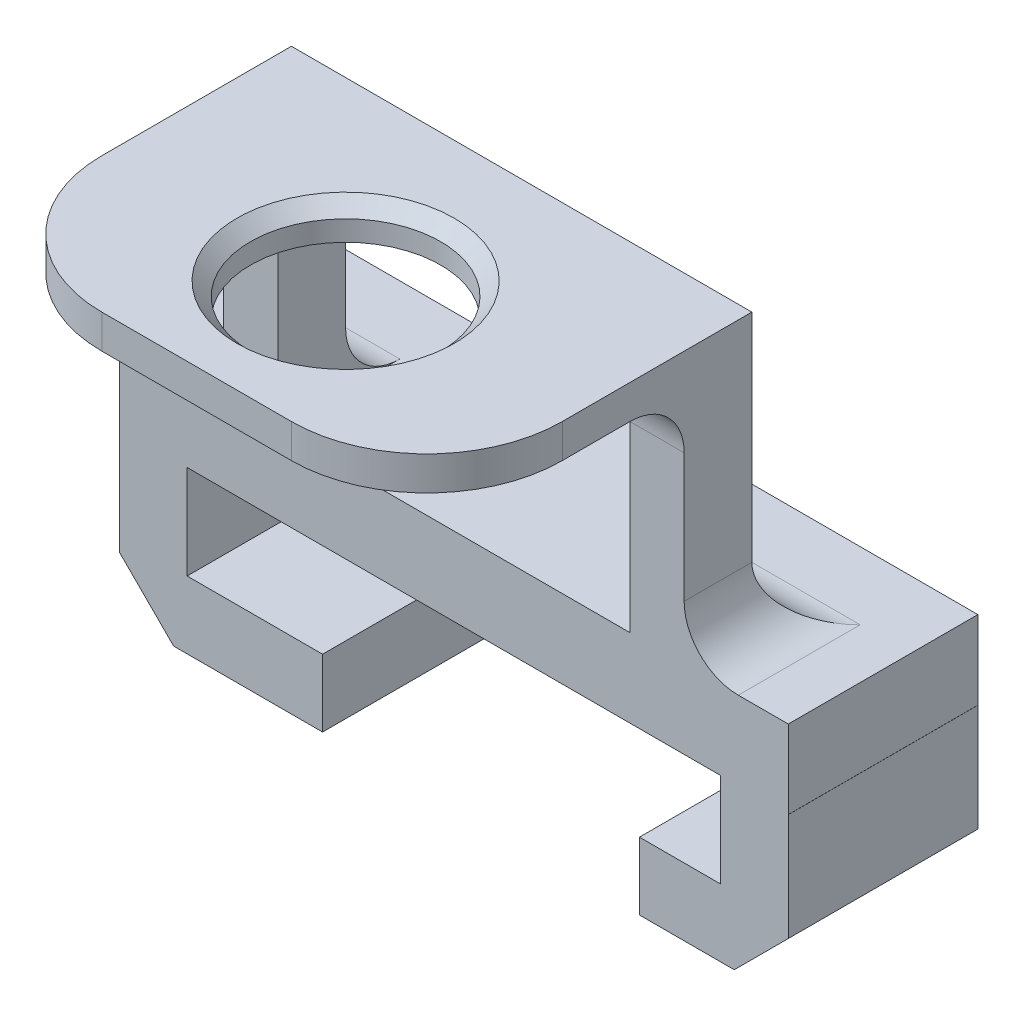
SolidWorks part; units mm, degrees
ref_plane "Front Plane" through (0, 0, 0) normal (0, 0, 1) x (1, 0, 0)
ref_plane "Top Plane" through (0, 0, 0) normal (0, 1, 0) x (1, 0, 0)
ref_plane "Right Plane" through (0, 0, 0) normal (1, 0, 0) x (0, 0, -1)
sketch "Sketch2" plane through (0, 0, 0) normal (0, 0, 1) x (1, 0, 0)
  line L0 (12.3453, 19.45) -> (-12.3453, 19.45)
  line L1 (12.3453, 22.3446) -> (-12.3453, 22.3446)
  line L2 (12.3453, 19.45) -> (12.3453, 22.3446)
  line L8 (-12.3453, 19.45) -> (-12.3453, 22.3446)
  dimension "D2" = 2.8946
extrude "Boss-Extrude2" add sketch "Sketch2" along normal blind 5
extrude "Boss-Extrude3" add sketch "Sketch2<2>" against normal blind 2
sketch "Sketch2<2>" plane through (0, 0, 0) normal (0, 0, 1) x (1, 0, 0) same geometry as "Sketch2"
ref_plane "Plane4" through (0, 0, 5) normal (0, 0, 1) x (1, 0, 0)
ref_plane "Plane6" through (0, 19.45, 0) normal (0, -1, 0) x (-1, 0, 0)
sketch "Sketch8" plane through (0, 19.45, 0) normal (0, -1, 0) x (-1, 0, 0)
  line L1 (-8.5825, -5) -> (8.5825, -5) construction
  line L2 (12.35, 2) -> (9.85, 2)
  line L3 (12.3453, 2) -> (-12.3453, 2) construction
  line L4 (-9.85, 2) -> (-9.85, -5)
  line L5 (-9.85, -5) -> (-12.35, -5)
  line L6 (-12.35, -5) -> (-12.35, 2)
  line L7 (-12.35, 2) -> (-9.85, 2)
  line L8 (12.35, -5) -> (12.35, 2)
  line L9 (9.85, -5) -> (12.35, -5)
  line L10 (9.85, 2) -> (9.85, -5)
  point P0 (0, 0)
  dimension "D1" = 9.85
  dimension "D2" = 9.85
  dimension "D3" = 2.5
  dimension "D4" = 2.5
extrude "Boss-Extrude4" add sketch "Sketch8" along normal blind 5.96
ref_plane "Plane7" through (9.85, 0, 0) normal (-1, 0, 0) x (0, 0, 1)
sketch "Sketch10" plane through (9.85, 0, 0) normal (-1, 0, 0) x (0, 0, 1)
  line L0 (5, 13.49) -> (-2, 13.49) construction
  line L1 (5, 13.49) -> (-2, 13.49)
  line L2 (5, 13.49) -> (5, 15.98)
  line L3 (5, 15.98) -> (-2, 15.98)
  line L4 (-2, 13.49) -> (-2, 15.98)
  line L5 (-2, 13.49) -> (-2, 19.45) construction
  dimension "D1" = 2.49
extrude "Boss-Extrude5" add sketch "Sketch10" along normal blind 3
ref_plane "Plane8" through (-9.85, 0, 0) normal (1, 0, 0) x (0, 0, -1)
sketch "Sketch11" plane through (-9.85, 0, 0) normal (1, 0, 0) x (0, 0, -1)
  line L0 (2, 13.49) -> (2, 19.45) construction
  line L1 (-5, 13.49) -> (2, 13.49)
  line L2 (-5, 13.49) -> (-5, 15.98)
  line L3 (-5, 15.98) -> (2, 15.98)
  line L4 (2, 13.49) -> (2, 15.98)
  dimension "D1" = 2.49
extrude "Boss-Extrude6" add sketch "Sketch11" along normal blind 5
ref_plane "Plane9" through (0, 22.3446, 0) normal (0, 1, 0) x (1, 0, 0)
sketch "Sketch12" plane through (0, 22.3446, 0) normal (0, 1, 0) x (1, 0, 0)
  line L3 (12.3453, -5) -> (-12.3453, -5) construction
  line L4 (8.5, -5) -> (-8.5, -5)
  line L5 (8.5, -5) -> (8.5, -2.5)
  line L6 (8.5, -2.5) -> (-8.5, -2.5)
  line L7 (-8.5, -5) -> (-8.5, -2.5)
  point P6 (0, 0)
  dimension "D1" = 17
  dimension "D2" = 8.5
  dimension "D3" = 2.5
extrude "Boss-Extrude7" add sketch "Sketch12" along normal blind 10
ref_plane "Plane10" through (0, 0, 5) normal (0, 0, 1) x (1, 0, 0)
sketch "Sketch14" plane through (0, 0, 5) normal (0, 0, 1) x (1, 0, 0)
  line L0 (-8.5, 32.3446) -> (8.5, 32.3446) construction
  line L2 (-8.5, 22.3446) -> (-12.3453, 22.3446) construction
  line L7 (-6.5, 31.0946) -> (6.5, 31.0946)
  line L8 (-6.5, 31.0946) -> (-6.5, 22.3446)
  line L9 (-6.5, 22.3446) -> (6.5, 22.3446)
  line L10 (6.5, 31.0946) -> (6.5, 22.3446)
  dimension "D1" = 1.25
  dimension "D2" = 0
extrude "Cut-Extrude7" cut sketch "Sketch14" against normal up to next
sketch "Sketch16" plane through (0, 0, 5) normal (0, 0, 1) x (1, 0, 0)
  line L0 (8.5, 32.3446) -> (8.5, 22.3446) construction
  line L1 (-8.5, 32.3446) -> (8.5, 32.3446)
  line L2 (-8.5, 32.3446) -> (-8.5, 31.0946)
  line L3 (-8.5, 31.0946) -> (8.5, 31.0946)
  line L4 (8.5, 32.3446) -> (8.5, 31.0946)
  dimension "D1" = 1.25
extrude "Boss-Extrude8" add sketch "Sketch16" along normal blind 9.5
ref_plane "Plane11" through (0, 32.3446, 0) normal (0, 1, 0) x (1, 0, 0)
sketch "Sketch17" plane through (0, 32.3446, 0) normal (0, 1, 0) x (1, 0, 0)
  line L0 (8.5, -14.5) -> (-8.5, -14.5) construction
  line L1 (-8.5, -2.5) -> (-8.5, -14.5) construction
  circle A0 centre (0, -9) radius 3.51
  dimension "D1" = 5.5
  dimension "D2" = 8.5
extrude "Cut-Extrude8" cut sketch "Sketch17" against normal up to next
fillet "Fillet7" radius 2 1 edges
fillet "Fillet8" radius 5 1 edges at (8.5, 31.7196, 14.5)
fillet "Fillet9" radius 5 1 edges at (-8.5, 31.7196, 14.5)
chamfer "Chamfer1" distance 2 angle 45 1 edges at (-12.35, 13.49, 1.5)
chamfer "Chamfer2" distance 2 angle 45 1 edges at (12.35, 13.49, 1.5)
ref_plane "Plane13" through (0, 0, 2.5) normal (0, 0, -1) x (-1, 0, 0)
sketch "Sketch22" plane through (0, 0, 2.5) normal (0, 0, -1) x (-1, 0, 0)
  line L1 (6.5, 22.3446) -> (8.5, 22.3446)
  line L2 (6.5, 22.3446) -> (6.5, 32.3446)
  line L3 (6.5, 32.3446) -> (8.5, 32.3446)
  line L4 (8.5, 22.3446) -> (8.5, 32.3446)
  line L5 (-6.5, 22.3446) -> (-8.5, 22.3446)
  line L6 (-6.5, 22.3446) -> (-6.5, 32.3446)
  line L7 (-6.5, 32.3446) -> (-8.5, 32.3446)
  line L8 (-8.5, 22.3446) -> (-8.5, 32.3446)
ref_plane "Plane14" through (-8.5, 0, 0) normal (-1, 0, 0) x (0, 0, 1)
fillet "Fillet11" radius 2 1 edges
fillet "Fillet12" radius 2 1 edges
fillet "Fillet13" radius 2 1 edges at (8.5, 22.3446, 2.5)
fillet "Fillet14" radius 2 1 edges at (-8.5, 22.3446, 2.5)
fillet "Fillet16" radius 2 1 edges
chamfer "Chamfer3" distance 0.5 angle 45 1 edges at (0, 32.3446, 12.51)
